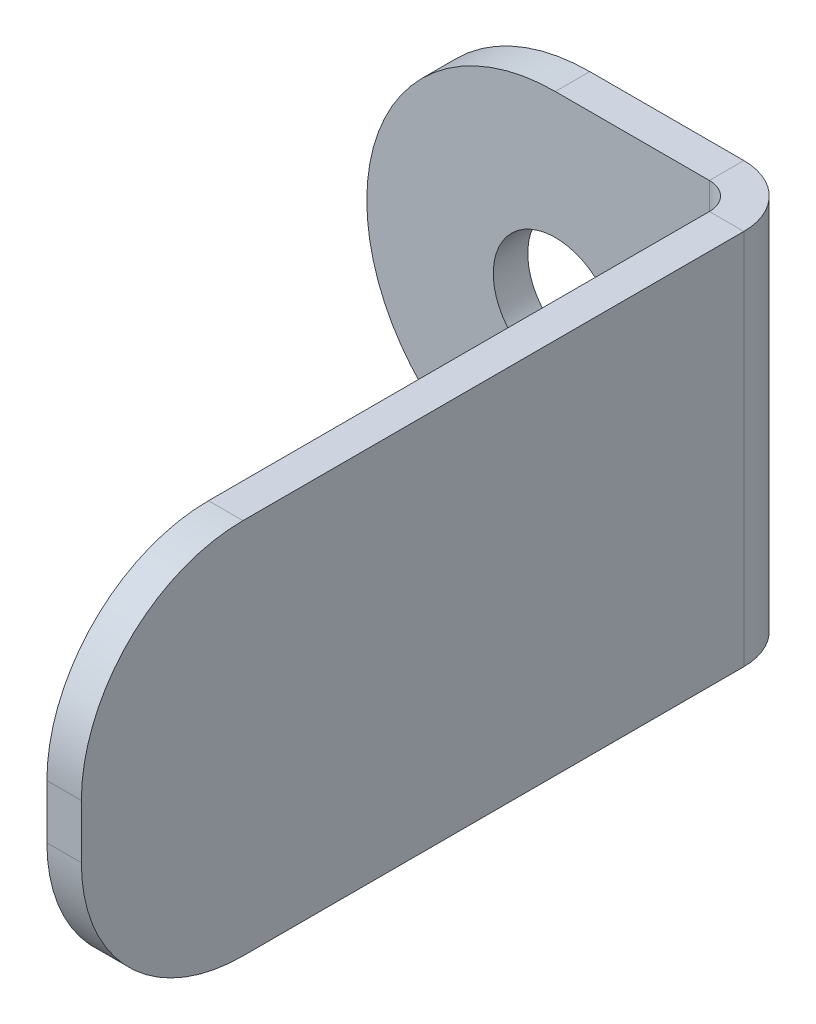
SolidWorks part; units mm, degrees
note: '?' marks a value the reader was unsure of. The reader was unsure of these and kept them because the rebuilt part matched: flange length of "Edge-Flange1".
material "AISI 4130 Steel, annealed at 865C"
ref_plane "Plane1" through (0, 0, 0) normal (0, 0, 1) x (1, 0, 0)
ref_plane "Plane2" through (0, 0, 0) normal (0, 1, 0) x (1, 0, 0)
ref_plane "Plane3" through (0, 0, 0) normal (1, 0, 0) x (0, 0, -1)
ref_axis "Axis1" through (-80.9, 0, 0) along (1, 0, 0)?
ref_axis "Axis2" through (0, 0, -80.9) along (0, 0, 1)?
ref_axis "Axis3" through (0, 50, 0) along (0, -1, 0)?
sketch "Sketch1" plane through (0, 0, 0) normal (0, 0, 1) x (1, 0, 0)
  line L0 (-12.7, 65.8812) -> (-6.35, 65.8812)
  line L1 (-6.35, 65.8812) -> (-6.35, 54.7687)
  line L2 (-6.35, 54.7687) -> (-12.7, 54.7687)
  circle A1 centre (-12.7, 60.325) radius 1.8288
  arc A2 (-12.7, 65.8812) -> (-12.7, 54.7687) centre (-12.7, 60.325) ccw
  dimension "D1" = 11.1125
  dimension "D2" = 6.35
base flange "Base-Flange1" sketch "Sketch1" thickness 1.016 reverse thickness direction yes parameters "D1"=4.7625
edge flange "Edge-Flange1" sketch "Sketch8" flange angle 90 flange length 20.32 flange position material inside bend radius 0.7937 thickness 1.016 relief rectangular parameters "D6"=10
sketch "Sketch8" plane through (-6.35, 0, 1.016) normal (1, 0, 0) x (0, 1, 0)
  line L0 (54.7687, 0) -> (65.8812, 0) construction
  line L1 (54.7687, 0) -> (65.8812, 0)
  line L2 (54.7687, 0) -> (54.7687, 20.32)
  line L3 (54.7687, 20.32) -> (65.8812, 20.32)
  line L4 (65.8812, 20.32) -> (65.8812, 0)
bend "EdgeBend1" bend radius 0.7937 bend angle 90 parameters "D5"=1
fillet "Fillet1" radius 4.7625 2 edges at (-6.858, 54.7687, 21.336) (-6.858, 65.8812, 21.336)
sketch "Bend-Lines1" [suppressed] plane through (0, 0, 0) normal (0, 1, 0) x (1, 0, 0)
sketch "Bounding-Box1" [suppressed] plane through (0, 0, 0) normal (0, 1, 0) x (1, 0, 0)
sheet metal parameters "Sheet-Metal5" thickness 1.016 parameters "D1"=4.7625
flat pattern "Flat-Pattern5" [suppressed]
sketch "Bend-Lines2" plane through (0, 0, 0) normal (0, 1, 0) x (1, 0, 0)
sketch3d "Bounding-Box2" [suppressed]
  line L0 (6.35, -6.35, 0) -> (6.35, 6.35, 0) construction
  line L1 (-6.3499, -6.35, 0) -> (-6.3499, 6.35, 0) construction
  line L2 (6.35, -6.35, 0) -> (-6.3499, -6.35, 0) construction
  line L3 (6.35, 6.35, 0) -> (-6.3499, 6.35, 0) construction
sheet metal parameters "Sheet-Metal6" thickness 1.016 parameters "D1"=4.7625
flat pattern "Flat-Pattern5"
sketch "Bend-Lines2" plane through (0, 0, 0) normal (0, 0, -1) x (-1, 0, 0)
  line L0 (7.1374, 65.8812) -> (7.1374, 54.7687) construction
  line L1 (7.1374, 65.8812) -> (7.1374, 54.7687) construction
sketch3d "Bounding-Box2" [suppressed]
  line L0 (5.5562, -5.5562, 0) -> (-26.1113, -5.5562, 0) construction
  line L1 (5.5562, 5.5562, 0) -> (-26.1113, 5.5562, 0) construction
  line L2 (5.5562, -5.5562, 0) -> (5.5562, 5.5562, 0) construction
  line L3 (-26.1113, -5.5562, 0) -> (-26.1113, 5.5562, 0) construction
bend of the flat pattern "Flatten-<EdgeBend1>1"
